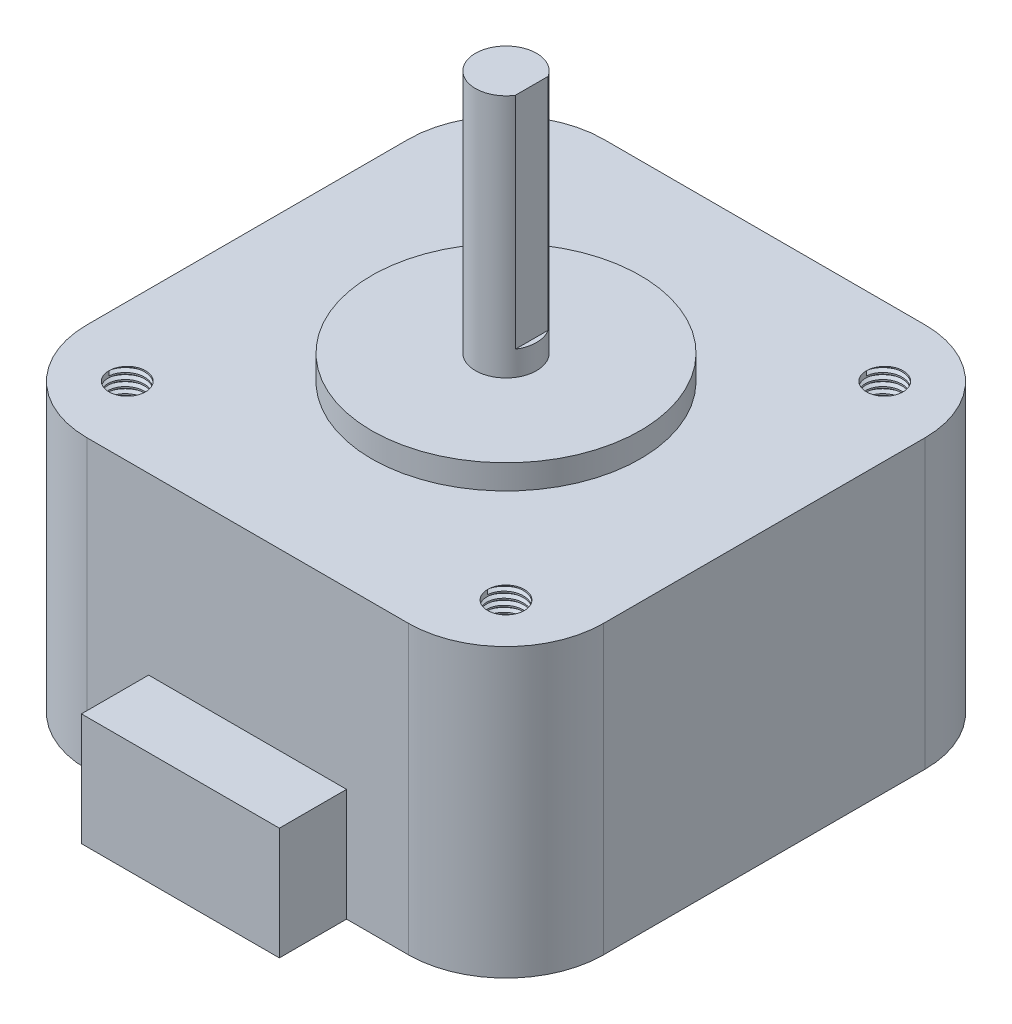
SolidWorks part; units mm, degrees
material "Alloy Steel"
ref_plane "Front Plane" through (0, 0, 0) normal (0, 0, 1) x (1, 0, 0)
ref_plane "Top Plane" through (0, 0, 0) normal (0, 1, 0) x (1, 0, 0)
ref_plane "Right Plane" through (0, 0, 0) normal (1, 0, 0) x (0, 0, -1)
sketch "Sketch1" plane through (0, 0, 0) normal (0, 1, 0) x (1, 0, 0)
  line L1 (0, 0) -> (42.3, 0)
  line L2 (0, 0) -> (0, 42.3)
  line L3 (0, 42.3) -> (42.3, 42.3)
  line L4 (42.3, 0) -> (42.3, 42.3)
  dimension "D1" = 42.3
  dimension "D2" = 42.3
extrude "Boss-Extrude1" add sketch "Sketch1" along normal blind 23.5
sketch "Sketch2" plane through (0, 23.5, 0) normal (0, 1, 0) x (1, 0, 0)
  line L0 (42.3, 42.3) -> (0, 42.3) construction
  line L1 (0, 42.3) -> (0, 0) construction
  circle A0 centre (21.15, 21.15) radius 11
  dimension "D3" = 22
  dimension "D1" = 21.15
  dimension "D2" = 21.15
extrude "Boss-Extrude2" add sketch "Sketch2" along normal blind 2
sketch "Sketch3" plane through (0, 25.5, 0) normal (0, 1, 0) x (1, 0, 0)
  circle A0 centre (21.15, 21.15) radius 2.5
  dimension "D1" = 5
extrude "Boss-Extrude3" add sketch "Sketch3" along normal blind 20
sketch "Sketch4" plane through (0, 45.5, 0) normal (0, 1, 0) x (1, 0, 0)
  line L3 (23.2594, 22.4919) -> (24.3262, 22.4919)
  line L4 (23.2594, 22.4919) -> (23.2594, 19.5694)
  line L5 (23.2594, 19.5694) -> (24.3262, 19.5694)
  line L6 (24.3262, 22.4919) -> (24.3262, 19.5694)
  circle A3 centre (21.15, 21.15) radius 2.5 construction
extrude "Cut-Extrude1" cut sketch "Sketch4" against normal blind 18
sketch "Sketch6" plane through (0, 23.5, 0) normal (0, 1, 0) x (1, 0, 0)
  line L0 (21.15, 42.3) -> (21.15, 0) construction
  line L1 (42.3, 42.3) -> (0, 42.3) construction
  line L2 (0, 0) -> (42.3, 0) construction
  line L3 (0, 42.3) -> (0, 0) construction
  circle A0 centre (5.65, 36.65) radius 1.5
  circle A1 centre (5.65, 5.65) radius 1.5
  circle A2 centre (36.65, 5.65) radius 1.5
  circle A3 centre (36.65, 36.65) radius 1.5
  dimension "D5" = 3
  dimension "D6" = 3
  dimension "D1" = 5.65
  dimension "D2" = 5.65
  dimension "D3" = 5.65
  dimension "D4" = 5.65
extrude "Cut-Extrude3" cut sketch "Sketch6" against normal blind 5
thread "Thread1" pitch 0.5 method cut profile "Thread Profile1" start angle 0, offset 0, length 10, pitch 0.5, diameter 3
ref_plane "Plane1" through (35.15, 23.5, -36.65) normal (0, 0, 1) x (-1, 0, 0)
sketch "Thread Profile1" plane through (35.15, 23.5, -36.65) normal (0, 0, 1) x (-1, 0, 0)
  line L0 (0, 0) -> (0, 0.5) construction
  line L1 (0, 0) -> (0.2706, 0.1562)
  line L2 (0.2706, 0.1562) -> (0.2706, 0.2187)
  line L3 (0.2706, 0.2187) -> (0, 0.375)
  line L4 (0.2706, 0.1875) -> (0, 0.1875) construction
  line L11 (0, 0) -> (0, 0.375)
  point P2 (0, 0)
  dimension "Pitch" = 0.5
  dimension "Profile_Angle" = 60
  dimension "Profile_Land" = 0.0625
  dimension "Profile_Height" = 0.2706
thread "Thread2" pitch 0.5 method cut profile "Thread Profile2" start angle 0, offset 0, length 10, pitch 0.5, diameter 3
ref_plane "Plane2" through (4.15, 23.5, -36.65) normal (0, 0, 1) x (-1, 0, 0)
sketch "Thread Profile2" plane through (4.15, 23.5, -36.65) normal (0, 0, 1) x (-1, 0, 0)
  line L0 (0, 0) -> (0, 0.5) construction
  line L1 (0, 0) -> (0.2706, 0.1562)
  line L2 (0.2706, 0.1562) -> (0.2706, 0.2187)
  line L3 (0.2706, 0.2187) -> (0, 0.375)
  line L4 (0.2706, 0.1875) -> (0, 0.1875) construction
  line L11 (0, 0) -> (0, 0.375)
  point P2 (0, 0)
  dimension "Pitch" = 0.5
  dimension "Profile_Angle" = 60
  dimension "Profile_Land" = 0.0625
  dimension "Profile_Height" = 0.2706
thread "Thread3" pitch 0.5 method cut profile "Thread Profile3" start angle 0, offset 0, length 10, pitch 0.5, diameter 3
ref_plane "Plane3" through (4.15, 23.5, -5.65) normal (0, 0, 1) x (-1, 0, 0)
sketch "Thread Profile3" plane through (4.15, 23.5, -5.65) normal (0, 0, 1) x (-1, 0, 0)
  line L0 (0, 0) -> (0, 0.5) construction
  line L1 (0, 0) -> (0.2706, 0.1562)
  line L2 (0.2706, 0.1562) -> (0.2706, 0.2187)
  line L3 (0.2706, 0.2187) -> (0, 0.375)
  line L4 (0.2706, 0.1875) -> (0, 0.1875) construction
  line L11 (0, 0) -> (0, 0.375)
  point P2 (0, 0)
  dimension "Pitch" = 0.5
  dimension "Profile_Angle" = 60
  dimension "Profile_Land" = 0.0625
  dimension "Profile_Height" = 0.2706
thread "Thread4" pitch 0.5 method cut profile "Thread Profile4" start angle 0, offset 0, length 10, pitch 0.5, diameter 3
ref_plane "Plane4" through (35.15, 23.5, -5.65) normal (0, 0, 1) x (-1, 0, 0)
sketch "Thread Profile4" plane through (35.15, 23.5, -5.65) normal (0, 0, 1) x (-1, 0, 0)
  line L0 (0, 0) -> (0, 0.5) construction
  line L1 (0, 0) -> (0.2706, 0.1562)
  line L2 (0.2706, 0.1562) -> (0.2706, 0.2187)
  line L3 (0.2706, 0.2187) -> (0, 0.375)
  line L4 (0.2706, 0.1875) -> (0, 0.1875) construction
  line L11 (0, 0) -> (0, 0.375)
  point P2 (0, 0)
  dimension "Pitch" = 0.5
  dimension "Profile_Angle" = 60
  dimension "Profile_Land" = 0.0625
  dimension "Profile_Height" = 0.2706
fillet "Fillet1" radius 8 4 edges at (0, 11.75, 0) (42.3, 11.75, 0) (42.3, 11.75, -42.3) (0, 11.75, -42.3)
sketch "Sketch16" plane through (0, 0, 0) normal (0, 0, 1) x (1, 0, 0)
  line L0 (8, 0) -> (34.3, 0) construction
  line L1 (13.05, 9.2) -> (29.25, 9.2)
  line L2 (13.05, 9.2) -> (13.05, 0)
  line L3 (13.05, 0) -> (29.25, 0)
  line L4 (29.25, 9.2) -> (29.25, 0)
  line L5 (21.15, 23.5) -> (21.15, 0) construction
  line L6 (8, 23.5) -> (34.3, 23.5) construction
  dimension "D1" = 9.2
  dimension "D2" = 8.1
  dimension "D3" = 8.1
extrude "Boss-Extrude4" add sketch "Sketch16" along normal blind 5.5
ref_plane "Plane5" through (0, 0, 0) normal (0, -1, 0) x (-1, 0, 0)
ref_plane "Plane6" through (0, 45.5, 0) normal (0, 1, 0) x (1, 0, 0)
